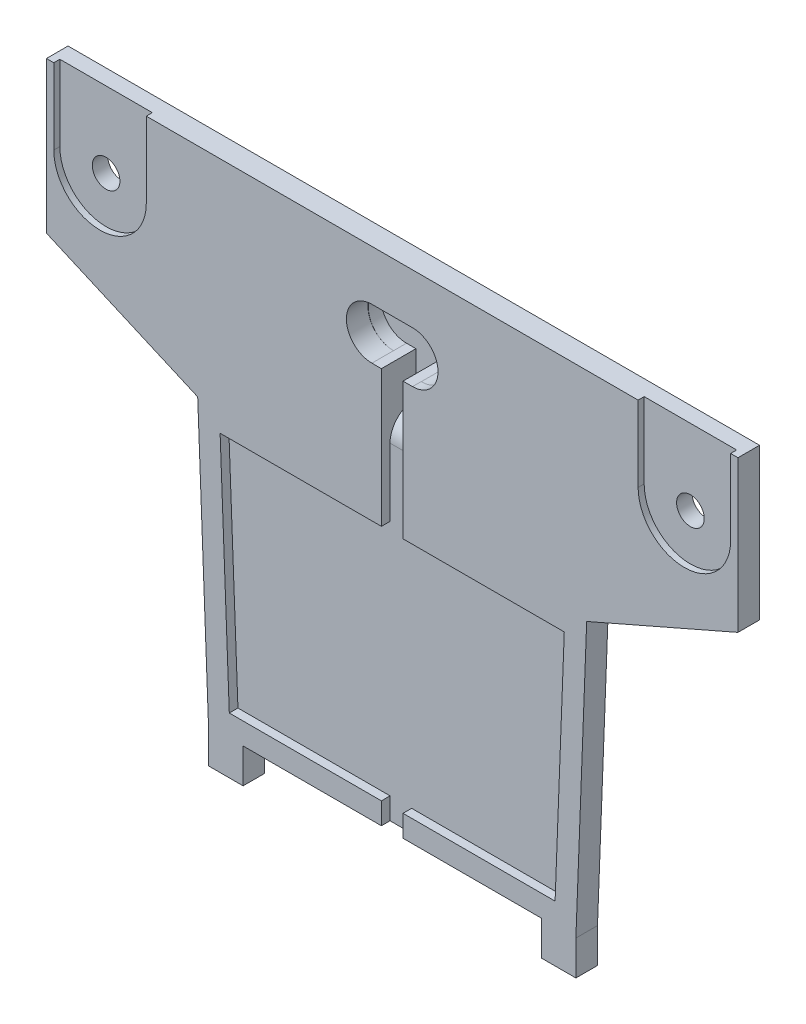
SolidWorks part; units mm, degrees
ref_plane "Front Plane" through (0, 0, 0) normal (0, 0, 1) x (1, 0, 0)
ref_plane "Top Plane" through (0, 0, 0) normal (0, 1, 0) x (1, 0, 0)
ref_plane "Right Plane" through (0, 0, 0) normal (1, 0, 0) x (0, 0, -1)
sketch "Sketch1" plane through (0, 0, 0) normal (0, 0, 1) x (1, 0, 0)
  line L0 (-53.975, 0) -> (53.975, 0)
  line L1 (53.975, 0) -> (57.15, 82.1613)
  line L2 (57.15, 82.1613) -> (101.6, 101.6)
  line L3 (101.6, 101.6) -> (101.6, 146.05)
  line L4 (101.6, 146.05) -> (-101.6, 146.05)
  line L5 (-101.6, 146.05) -> (-101.6, 101.6)
  line L6 (-101.6, 101.6) -> (-57.15, 82.1613)
  line L7 (-57.15, 82.1613) -> (-53.975, 0)
  point P4 (0, 0)
  point P5 (0, 0)
  point P11 (0, 146.05)
  point P12 (0, 0)
  dimension "D1" = 44.45
  dimension "D2" = 44.45
  dimension "D3" = 146.05
  dimension "D4" = 107.95
  dimension "D5" = 203.2
  dimension "D6" = 114.3
base flange "Main Body" sketch "Sketch1" thickness 6.35 reverse thickness direction no parameters "D1"=1
sketch "Sketch7" plane through (0, 0, 0) normal (0, 0, 1) x (1, 0, 0)
  line L0 (-50.5649, 76.2) -> (-47.8656, 6.35)
  line L1 (-47.8656, 6.35) -> (47.8656, 6.35)
  line L2 (47.8656, 6.35) -> (50.5649, 76.2)
  line L3 (50.5649, 76.2) -> (-50.5649, 76.2)
  line L4 (-57.15, 82.1613) -> (-53.975, 0) construction
  line L8 (-53.975, 0) -> (53.975, 0) construction
  line L9 (53.975, 0) -> (57.15, 82.1613) construction
  point P2 (0, 6.35)
  point P5 (0, 76.2)
  dimension "D1" = 6.35
  dimension "D2" = 6.35
  dimension "D3" = 69.85
  dimension "D4" = 6.35
extrude "Battery Spacing" cut sketch "Sketch7" against normal blind 2.54 normal cut yes
sketch "Sketch8" plane through (0, 0, 0) normal (0, 0, 1) x (1, 0, 0)
  line L0 (-5.969, 131.318) -> (5.969, 131.318)
  line L1 (5.969, 116.332) -> (-5.969, 116.332)
  line L3 (101.6, 146.05) -> (-101.6, 146.05) construction
  arc A0 (5.969, 131.318) -> (5.969, 116.332) centre (5.969, 123.825) cw
  arc A1 (-5.969, 116.332) -> (-5.969, 131.318) centre (-5.969, 123.825) cw
  circle A2 centre (85.852, 123.825) radius 4.064
  circle A3 centre (-85.852, 123.825) radius 4.064
  point P5 (1.524, 123.825)
  point P7 (-1.524, 123.825)
  point P8 (0, 131.318)
  point P9 (0, 116.332)
  point P12 (-13.462, 123.825)
  point P13 (13.462, 123.825)
  point P16 (3.1018, 136.2181)
  point P17 (-8.8197, 130.1043)
  point P20 (4.0257, 123.825)
  point P21 (0, 146.05)
  dimension "D1" = 26.924
  dimension "D2" = 72.39
  dimension "D3" = 72.39
  dimension "D4" = 14.732
  dimension "D5" = 11.938
extrude "Light Sockets" cut sketch "Sketch8" against normal blind 12.7 normal cut yes
sketch "Sketch9" plane through (0, 0, -6.35) normal (0, 0, -1) x (-1, 0, 0)
  line L0 (-9.525, 111.7653) -> (-9.525, 99.0653)
  line L1 (-9.525, 99.0653) -> (9.525, 99.0653)
  line L2 (9.525, 99.0653) -> (9.525, 111.7653)
  line L3 (9.525, 111.7653) -> (9.1017, 112.1697)
  line L4 (5.969, 136.398) -> (-5.969, 136.398)
  line L5 (-5.969, 111.252) -> (5.969, 111.252)
  line L6 (5.969, 136.398) -> (-5.969, 136.398)
  arc A4 (5.969, 111.252) -> (5.969, 136.398) centre (5.969, 123.825) ccw
  arc A5 (-5.969, 136.398) -> (-5.969, 111.252) centre (-5.969, 123.825) ccw
  arc A6 (9.525, 111.7653) -> (5.969, 136.398) centre (5.969, 123.825) ccw
  arc A7 (-5.969, 136.398) -> (-9.525, 111.7653) centre (-5.969, 123.825) ccw
  dimension "D2" = 19.05
  dimension "D3" = 12.7
  dimension "D4" = 12.7
  dimension "D1" = 5.08
extrude "Light Leads Pocket" add sketch "Sketch9" along normal blind 6.35
sketch "Sketch10" plane through (0, 0, 0) normal (0, 0, 1) x (1, 0, 0)
  line L0 (-3.175, 116.332) -> (3.175, 116.332)
  line L1 (-5.969, 116.332) -> (5.969, 116.332) construction
  line L2 (-5.969, 116.332) -> (5.969, 116.332) construction
  line L3 (3.175, 116.332) -> (3.175, 76.2)
  line L4 (50.5649, 76.2) -> (-50.5649, 76.2) construction
  line L5 (3.175, 76.2) -> (3.175, 6.35)
  line L6 (-47.8656, 6.35) -> (47.8656, 6.35) construction
  line L7 (3.175, 6.35) -> (3.175, 0)
  line L8 (-53.975, 0) -> (53.975, 0) construction
  line L9 (3.175, 0) -> (-3.175, 0)
  line L10 (-3.175, 0) -> (-3.175, 116.332)
  point P6 (0, 116.332)
  dimension "D1" = 6.35
extrude "Wire Trail" cut sketch "Sketch10" against normal blind 2.54 normal cut yes
sketch "Sketch12" plane through (0, 0, -2.54) normal (0, 0, 1) x (1, 0, 0)
  line L0 (-3.175, 116.332) -> (-5.9601, 116.332)
  line L1 (3.175, 116.332) -> (3.175, 103.7305)
  line L2 (3.175, 76.2) -> (3.175, 116.332) construction
  line L3 (3.175, 103.7305) -> (-3.175, 103.7305)
  line L4 (-3.175, 116.332) -> (-3.175, 76.2) construction
  line L5 (-3.175, 103.7305) -> (-3.175, 116.332)
  line L6 (-3.175, 116.332) -> (-3.175, 76.2) construction
  line L7 (3.175, 76.2) -> (3.175, 116.332) construction
  line L8 (-5.9601, 131.1354) -> (6.0002, 131.1354)
  line L9 (6.0002, 116.332) -> (3.175, 116.332)
  arc A0 (-5.9601, 116.332) -> (-5.9601, 131.1354) centre (-5.9601, 123.7337) cw
  arc A1 (6.0002, 131.1354) -> (6.0002, 116.332) centre (6.0002, 123.7337) cw
extrude "Lead Room" cut sketch "Sketch12" against normal blind 7.62 normal cut yes
fillet "Fillet1" radius 7.62 1 edges at (0, 103.7305, -2.54)
sketch "Sketch13" plane through (0, 0, 0) normal (0, 0, 1) x (1, 0, 0)
  line L0 (72.263, 146.05) -> (72.263, 123.825)
  line L1 (101.6, 146.05) -> (-101.6, 146.05) construction
  line L2 (99.441, 123.825) -> (99.441, 146.05)
  line L3 (99.441, 146.05) -> (72.263, 146.05)
  arc A0 (72.263, 123.825) -> (99.441, 123.825) centre (85.852, 123.825) ccw
  circle A1 centre (85.852, 123.825) radius 4.064 construction
  point P6 (0, 0)
  dimension "D1" = 27.178
extrude "Tab Slots" cut sketch "Sketch13" against normal blind 1.778 normal cut yes
mirror "Mirror1" about plane through (0, 0, 0) normal (1, 0, 0) of "Tab Slots"
sketch "Sketch14" plane through (0, 0, 0) normal (0, -1, 0) x (1, 0, 0)
  line L0 (3.175, 0) -> (53.975, 0) construction
  line L1 (43.815, 0) -> (53.975, 0)
  line L2 (43.815, 0) -> (43.815, -6.35)
  line L3 (43.815, -6.35) -> (53.975, -6.35)
  line L4 (53.975, 0) -> (53.975, -6.35)
  dimension "D1" = 10.16
extrude "Screw Mount" add sketch "Sketch14" along normal blind 10.16
mirror "Mirror2" about plane through (0, 0, 0) normal (1, 0, 0) of "Screw Mount"
sketch "Bend-Lines1" [suppressed] plane through (0, 0, 0) normal (0, 1, 0) x (1, 0, 0)
sketch "Bounding-Box1" [suppressed] plane through (0, 0, 0) normal (0, 1, 0) x (1, 0, 0)
sheet metal parameters "Sheet-Metal1" thickness 6.35 parameters "D1"=1
flat pattern "Flat-Pattern1" [suppressed]
sketch "Bend-Lines2" plane through (0, 0, 0) normal (0, 1, 0) x (1, 0, 0)
sketch3d "Bounding-Box2" [suppressed]
  line L0 (101.6, 0, 0) -> (-101.6, 0, 0) construction
  line L1 (101.6, 146.05, 0) -> (-101.6, 146.05, 0) construction
  line L2 (101.6, 0, 0) -> (101.6, 146.05, 0) construction
  line L3 (-101.6, 0, 0) -> (-101.6, 146.05, 0) construction
sheet metal parameters "Sheet-Metal2" thickness 6.35 parameters "D1"=1
flat pattern "Flat-Pattern1"
sketch "Bend-Lines2" plane through (0, 0, 0) normal (0, 1, 0) x (1, 0, 0)
sketch3d "Bounding-Box2" [suppressed]
  line L0 (-101.6, 0, 0) -> (101.6, 0, 0) construction
  line L1 (-101.6, 146.05, 0) -> (101.6, 146.05, 0) construction
  line L2 (-101.6, 0, 0) -> (-101.6, 146.05, 0) construction
  line L3 (101.6, 0, 0) -> (101.6, 146.05, 0) construction
sheet metal parameters "Sheet-Metal3" thickness 6.35 parameters "D1"=1
flat pattern "Flat-Pattern1"
sketch "Bend-Lines2" plane through (0, 0, 0) normal (0, 1, 0) x (1, 0, 0)
sketch3d "Bounding-Box2" [suppressed]
  line L0 (-101.6, 0, 0) -> (101.6, 0, 0) construction
  line L1 (-101.6, 146.05, 0) -> (101.6, 146.05, 0) construction
  line L2 (-101.6, 0, 0) -> (-101.6, 146.05, 0) construction
  line L3 (101.6, 0, 0) -> (101.6, 146.05, 0) construction
sheet metal parameters "Sheet-Metal4" thickness 6.35 parameters "D1"=1
flat pattern "Flat-Pattern1"
sketch "Bend-Lines2" plane through (0, 0, 0) normal (0, 1, 0) x (1, 0, 0)
sketch3d "Bounding-Box2" [suppressed]
  line L0 (-101.6, 0, 0) -> (101.6, 0, 0) construction
  line L1 (-101.6, 146.05, 0) -> (101.6, 146.05, 0) construction
  line L2 (-101.6, 0, 0) -> (-101.6, 146.05, 0) construction
  line L3 (101.6, 0, 0) -> (101.6, 146.05, 0) construction
sheet metal parameters "Sheet-Metal5" thickness 6.35 parameters "D1"=1
flat pattern "Flat-Pattern1"
sketch "Bend-Lines2" plane through (0, 0, 0) normal (0, 1, 0) x (1, 0, 0)
sketch3d "Bounding-Box2" [suppressed]
  line L0 (-101.6, 0, 0) -> (101.6, 0, 0) construction
  line L1 (-101.6, 146.05, 0) -> (101.6, 146.05, 0) construction
  line L2 (-101.6, 0, 0) -> (-101.6, 146.05, 0) construction
  line L3 (101.6, 0, 0) -> (101.6, 146.05, 0) construction
sheet metal parameters "Sheet-Metal6" thickness 6.35 parameters "D1"=1
flat pattern "Flat-Pattern1"
sketch "Bend-Lines2" plane through (0, 0, 0) normal (0, 1, 0) x (1, 0, 0)
sketch3d "Bounding-Box2" [suppressed]
  line L0 (-101.6, 0, 0) -> (101.6, 0, 0) construction
  line L1 (-101.6, 146.05, 0) -> (101.6, 146.05, 0) construction
  line L2 (-101.6, 0, 0) -> (-101.6, 146.05, 0) construction
  line L3 (101.6, 0, 0) -> (101.6, 146.05, 0) construction
sheet metal parameters "Sheet-Metal7" thickness 6.35 parameters "D1"=1
flat pattern "Flat-Pattern1"
sketch "Bend-Lines2" plane through (0, 0, 0) normal (0, 1, 0) x (1, 0, 0)
sketch3d "Bounding-Box2" [suppressed]
  line L0 (-101.6, 0, 0) -> (101.6, 0, 0) construction
  line L1 (-101.6, 146.05, 0) -> (101.6, 146.05, 0) construction
  line L2 (-101.6, 0, 0) -> (-101.6, 146.05, 0) construction
  line L3 (101.6, 0, 0) -> (101.6, 146.05, 0) construction
sheet metal parameters "Sheet-Metal8" thickness 6.35 parameters "D1"=1
flat pattern "Flat-Pattern1"
sketch "Bend-Lines2" plane through (0, 0, 0) normal (0, 1, 0) x (1, 0, 0)
sketch3d "Bounding-Box2" [suppressed]
  line L0 (-101.6, 0, 0) -> (101.6, 0, 0) construction
  line L1 (-101.6, 146.05, 0) -> (101.6, 146.05, 0) construction
  line L2 (-101.6, 0, 0) -> (-101.6, 146.05, 0) construction
  line L3 (101.6, 0, 0) -> (101.6, 146.05, 0) construction
sheet metal parameters "Sheet-Metal9" thickness 6.35 parameters "D1"=1
flat pattern "Flat-Pattern1"
sketch "Bend-Lines2" plane through (0, 0, 0) normal (0, 1, 0) x (1, 0, 0)
sketch3d "Bounding-Box2" [suppressed]
  line L0 (-101.6, -10.16, 0) -> (101.6, -10.16, 0) construction
  line L1 (-101.6, 146.05, 0) -> (101.6, 146.05, 0) construction
  line L2 (-101.6, -10.16, 0) -> (-101.6, 146.05, 0) construction
  line L3 (101.6, -10.16, 0) -> (101.6, 146.05, 0) construction
sheet metal parameters "Sheet-Metal10" thickness 6.35 parameters "D1"=1
flat pattern "Flat-Pattern1"
sketch "Bend-Lines2" plane through (0, 0, 0) normal (0, 1, 0) x (1, 0, 0)
sketch3d "Bounding-Box2" [suppressed]
  line L0 (-101.6, -10.16, 0) -> (101.6, -10.16, 0) construction
  line L1 (-101.6, 146.05, 0) -> (101.6, 146.05, 0) construction
  line L2 (-101.6, -10.16, 0) -> (-101.6, 146.05, 0) construction
  line L3 (101.6, -10.16, 0) -> (101.6, 146.05, 0) construction
